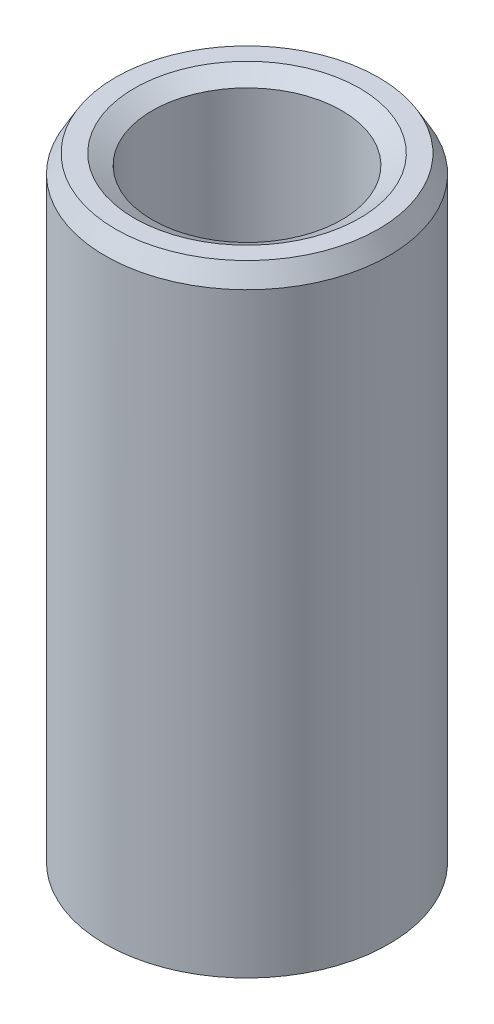
SolidWorks part; units mm, degrees
ref_plane "Front Plane" through (0, 0, 0) normal (0, 0, 1) x (1, 0, 0)
ref_plane "Top Plane" through (0, 0, 0) normal (0, 1, 0) x (1, 0, 0)
ref_plane "Right Plane" through (0, 0, 0) normal (1, 0, 0) x (0, 0, -1)
sketch "Sketch1" plane through (0, 0, 0) normal (0, 1, 0) x (1, 0, 0)
  circle A0 centre (0, 0) radius 27.5
  dimension "SLEEVE_OD" = 55
extrude "Boss-Extrude1" add sketch "Sketch1" along normal blind 121.052
sketch "Sketch2" plane through (0, 0, 0) normal (0, 1, 0) x (1, 0, 0)
  circle A0 centre (0, 0) radius 18.3626
  dimension "BORE_D" = 36.7252
extrude "Cut-Extrude1" cut sketch "Sketch2" along normal through all
chamfer "Chamfer1" distance 3.4803 angle 30 4 edges at (0, 121.052, 18.3626) (0, 0, 18.3626) (0, 0, 27.5) (0, 121.052, 27.5) first distance on face at (0, 121.052, 18.3626) first distance on face at (0, 0, 18.3626) first distance on face at (0, 121.052, 27.5)
